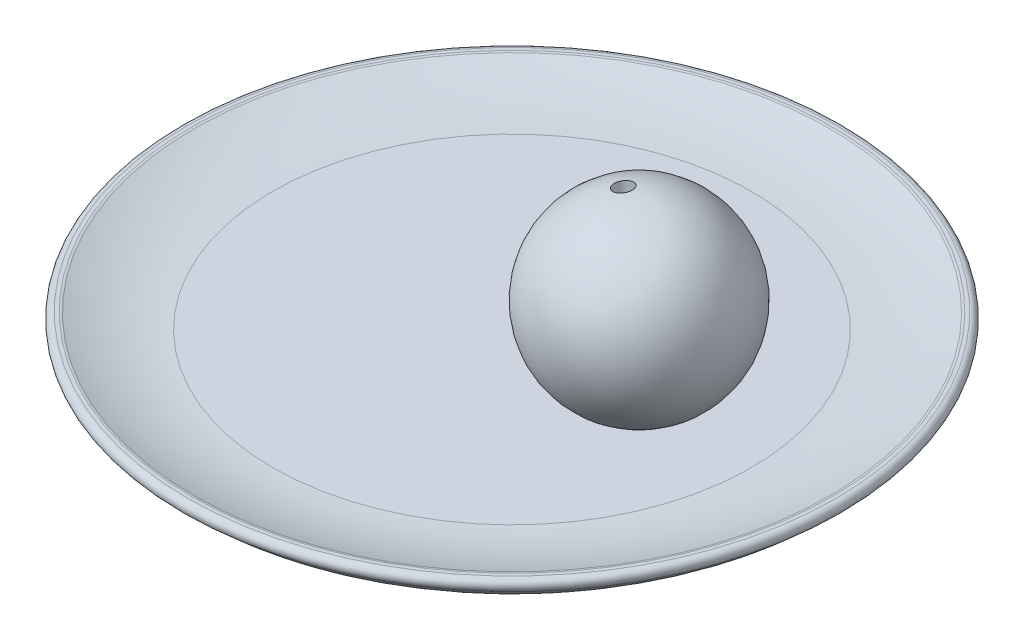
SolidWorks part; units mm, degrees
ref_plane "Front Plane" through (0, 0, 0) normal (0, 0, 1) x (1, 0, 0)
ref_plane "Top Plane" through (0, 0, 0) normal (0, 1, 0) x (1, 0, 0)
ref_plane "Right Plane" through (0, 0, 0) normal (1, 0, 0) x (0, 0, -1)
sketch "Sketch1" plane through (0, 0, 0) normal (0, 1, 0) x (1, 0, 0)
  circle A0 centre (0, 0) radius 55
  dimension "D1" = 110
extrude "Boss-Extrude1" add sketch "Sketch1" along normal blind 7.5
sketch "Sketch2" plane through (0, 7.5, 0) normal (0, 1, 0) x (1, 0, 0)
  circle A2 centre (0, 0) radius 52
  circle A3 centre (0, 0) radius 52
  dimension "D1" = 3
extrude "Cut-Extrude1" cut sketch "Sketch2" against normal blind 2.5
fillet "Fillet1" radius 35 1 edges at (0, 5, 52)
fillet "Fillet3" radius 20 1 edges at (0, 0, 55)
fillet "Fillet4" radius 1 2 edges at (0, 7.5, 55) (0, 7.5, 52)
sketch "Sketch3" plane through (0, 0, 0) normal (0, 0, 1) x (1, 0, 0)
  line L0 (20.7267, 4.5108) -> (20.7267, 34.5108) construction
  line L1 (20.7267, 4.5108) -> (20.7267, 34.5108)
  line L2 (39.0096, 5) -> (-39.0096, 5) construction
  arc A0 (20.7267, 34.5108) -> (20.7267, 4.5108) centre (20.7267, 19.5108) cw
  point P3 (24.5264, 5)
  dimension "D2" = 20.7267
  dimension "D1" = 30
  dimension "D3" = 0.4892
revolve "Revolve1" add sketch "Sketch3" angle 360 about L0
sketch "Sketch4" plane through (0, 0, 0) normal (0, 0, 1) x (1, 0, 0)
  line L0 (20.7267, 32.0108) -> (20.7267, 19.5108) construction
  line L1 (20.7267, 19.5108) -> (-26.1583, 285.4088) construction
  line L2 (-39.3875, 0) -> (39.3875, 0) construction
  line L3 (-26.1583, 285.4088) -> (-26.1583, 19.5108) construction
  line L4 (-26.1583, 19.5108) -> (20.7267, 19.5108) construction
  circle A0 centre (20.7267, 19.5108) radius 15 construction
  dimension "D1" = 270
  dimension "D2" = 80
ref_plane "Plane1" through (-5.3163, 30.1501, 0) normal (-0.1736, 0.9848, 0) x (0.9848, 0.1736, 0)
sketch "Sketch5" plane through (-5.3163, 30.1501, 0) normal (-0.1736, 0.9848, 0) x (0.9848, 0.1736, 0)
  line L0 (-22.3729, 0) -> (23.7998, 0) construction
  line L1 (25.9704, 0) -> (23.7998, 0) construction
  circle A0 centre (23.7998, 0) radius 1.5
  dimension "D1" = 3
extrude "Cut-Extrude2" cut sketch "Sketch5" against normal up to vertex (15 mm away) up to point (20.7267, 19.5108, 0)
